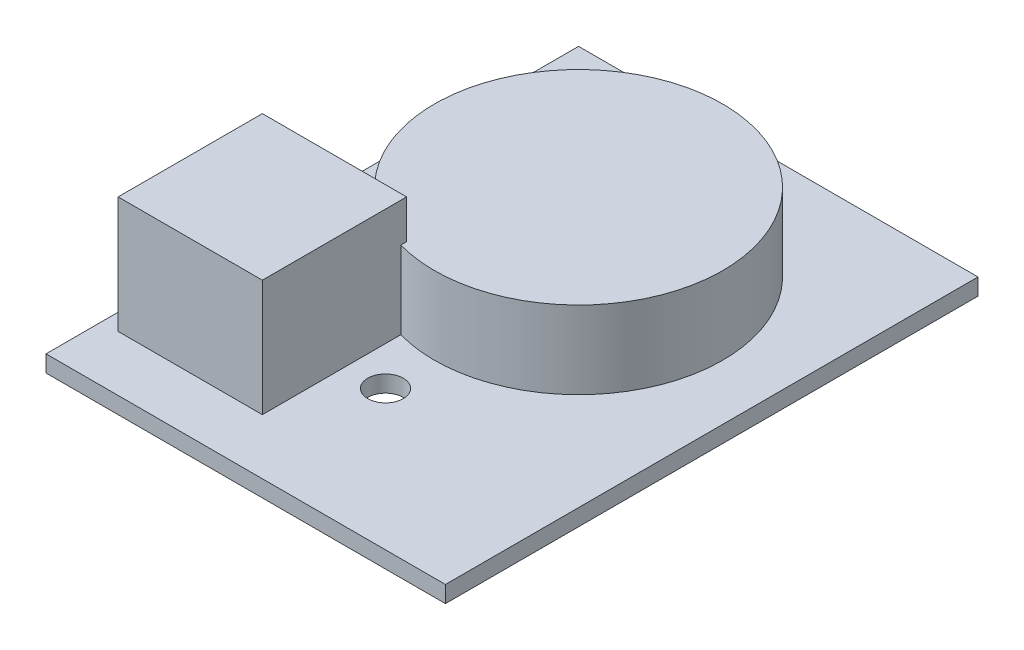
SolidWorks part; units mm, degrees
ref_plane "Front Plane" through (0, 0, 0) normal (0, 0, 1) x (1, 0, 0)
ref_plane "Top Plane" through (0, 0, 0) normal (0, 1, 0) x (1, 0, 0)
ref_plane "Right Plane" through (0, 0, 0) normal (1, 0, 0) x (0, 0, -1)
sketch "Sketch1" plane through (0, 0, 0) normal (0, 1, 0) x (1, 0, 0)
  line L0 (-3.5, -6) -> (-3.5, -19)
  line L1 (-15, -21) -> (15, -21)
  line L2 (-15, -21) -> (-15, 21)
  line L3 (-15, 21) -> (15, 21)
  line L4 (15, -21) -> (15, 21)
  line L5 (-15, -21) -> (15, 21) construction
  line L6 (-15, 21) -> (15, -21) construction
  line L7 (-15, -7.5) -> (-5, -7.5)
  line L8 (-15, -7.5) -> (-15, -17.5)
  line L9 (-15, -17.5) -> (-5, -17.5)
  line L10 (-5, -7.5) -> (-5, -17.5)
  line L11 (-16.5, -19) -> (-3.5, -19)
  line L12 (-16.5, -6) -> (-16.5, -19)
  line L13 (-16.5, -6) -> (-3.5, -6)
  line L14 (-18, -24) -> (-18, 24)
  line L15 (-18, 24) -> (18, 24)
  line L16 (18, -24) -> (18, 24)
  line L17 (-18, -24) -> (18, -24)
  circle A0 centre (0, 6) radius 11.5
  circle A1 centre (0, 6) radius 13
  circle A2 centre (0, -11.4) radius 1.6
  point P0 (0, 0)
  point P24 (0, 0)
  dimension "D3" = 23
  dimension "D10" = 3.2
  dimension "D1" = 42
  dimension "D2" = 30
  dimension "D4" = 15
  dimension "D5" = 10
  dimension "D6" = 10
  dimension "D7" = 3.5
  dimension "D11" = 9.6
  dimension "D8" = 1.5
  dimension "D9" = 3
extrude "Boss-Extrude1" add sketch "Sketch1" along normal blind 1.5 contours L15 L16 L17 L14
extrude "Boss-Extrude2" add sketch "Sketch1<3>" along normal blind 8.5 contours A1
sketch "Sketch1<3>" plane through (0, 0, 0) normal (0, 1, 0) x (1, 0, 0) same geometry as "Sketch1"
extrude "Boss-Extrude3" add sketch "Sketch1<4>" along normal blind 12 contours L0 L11 L12 L13
sketch "Sketch1<4>" plane through (0, 0, 0) normal (0, 1, 0) x (1, 0, 0) same geometry as "Sketch1"
extrude "Cut-Extrude2" cut sketch "Sketch1<5>" along normal through all contours A2 region at (0, 0, 11.4)
sketch "Sketch1<5>" plane through (0, 0, 0) normal (0, 1, 0) x (1, 0, 0) same geometry as "Sketch1"
equation "\"D4@Sketch1\"=3.5+(\"D3@Sketch1\"/2)"
equation "\"D11@Sketch1\"=8+(\"D10@Sketch1\"/2)"
